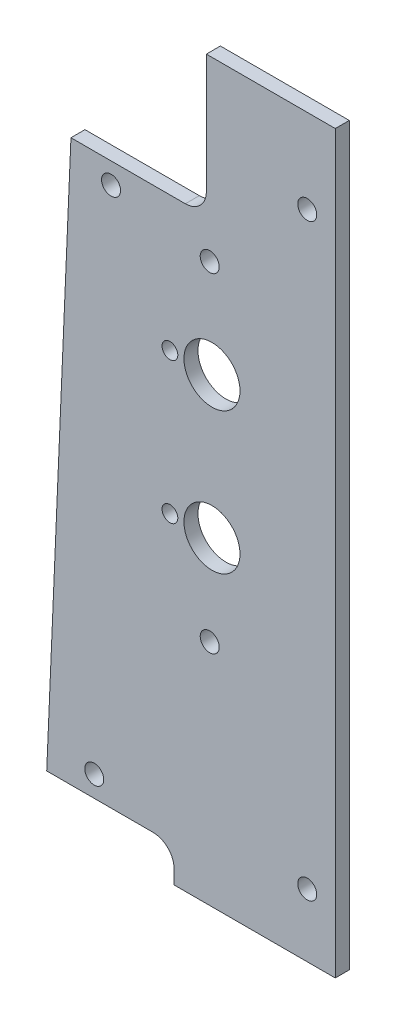
SolidWorks part; units mm, degrees
material "Acrylic (Medium-high impact)"
ref_plane "Front Plane" through (0, 0, 0) normal (0, 0, 1) x (1, 0, 0)
ref_plane "Top Plane" through (0, 0, 0) normal (0, 1, 0) x (1, 0, 0)
ref_plane "Right Plane" through (0, 0, 0) normal (1, 0, 0) x (0, 0, -1)
sketch "Sketch1" plane through (0, 0, 0) normal (0, 0, 1) x (1, 0, 0)
  line L8 (-36.5125, 0) -> (0, 0)
  line L9 (0, 0) -> (0, 166.6875)
  line L10 (0, 166.6875) -> (-29.21, 166.6875)
  line L11 (-29.21, 166.6875) -> (-29.21, 139.7)
  line L12 (-33.9725, 134.9375) -> (-59.8907, 134.9375)
  line L13 (-59.8907, 134.9375) -> (-65.3795, 7.9375)
  line L14 (-65.3795, 7.9375) -> (-41.275, 7.9375)
  line L15 (-36.5125, 3.175) -> (-36.5125, 0)
  line L16 (-36.5125, 0) -> (0, 0)
  line L17 (0, 0) -> (0, 166.6875)
  line L18 (0, 166.6875) -> (-29.21, 166.6875)
  line L19 (-29.21, 166.6875) -> (-29.21, 139.7)
  line L20 (-33.9725, 134.9375) -> (-59.8907, 134.9375)
  line L21 (-59.8907, 134.9375) -> (-65.3795, 7.9375)
  line L22 (-65.3795, 7.9375) -> (-41.275, 7.9375)
  line L23 (-36.5125, 3.175) -> (-36.5125, 0)
  arc A2 (-33.9725, 134.9375) -> (-29.21, 139.7) centre (-33.9725, 139.7) ccw
  arc A3 (-36.5125, 3.175) -> (-41.275, 7.9375) centre (-41.275, 3.175) ccw
  arc A4 (-33.9725, 134.9375) -> (-29.21, 139.7) centre (-33.9725, 139.7) ccw
  arc A5 (-36.5125, 3.175) -> (-41.275, 7.9375) centre (-41.275, 3.175) ccw
  dimension "D1" = 0
extrude "Boss-Extrude1" add sketch "Sketch1" against normal blind 3.175
hole_wizard "9/64 (0.14063) Diameter Hole1" positions "Sketch6" profile "Sketch5" hole size "9/64" standard "ANSI Inch" end condition through all
sketch "Sketch6" plane through (0, 0, 0) normal (0, 0, 1) x (1, 0, 0)
  point P0 (-18.415, 26.3525)
  point P3 (-37.465, 72.39)
  point P6 (-37.465, 104.394)
sketch "Sketch5" plane through (-18.415, 26.3525, 0) normal (1, 0, 0) x (0, -1, 0)
  line L0 (0, 0) -> (0, 3.175)
  line L1 (0, 3.175) -> (1.786, 3.175)
  line L2 (1.786, 3.175) -> (1.786, 0)
  line L5 (1.786, 0) -> (0, 0)
  line L11 (0, -6.35) -> (0, 107.95) construction
  dimension "Thru Hole Dia." = 3.572
  dimension "Thru Hole Depth" = 3.175
hole_wizard "1/2 (0.5) Diameter Hole1" positions "Sketch8" profile "Sketch7" hole size "1/2" standard "ANSI Inch" end condition through all
sketch "Sketch8" plane through (0, 0, 0) normal (0, 0, 1) x (1, 0, 0)
  point P0 (-27.94, 26.3525)
  point P3 (-27.94, 72.39)
  point P6 (-27.94, 104.394)
sketch "Sketch7" plane through (-27.94, 26.3525, 0) normal (1, 0, 0) x (0, -1, 0)
  line L0 (0, 0) -> (0, 3.175)
  line L1 (0, 3.175) -> (6.35, 3.175)
  line L2 (6.35, 3.175) -> (6.35, 0)
  line L5 (6.35, 0) -> (0, 0)
  line L11 (0, -6.35) -> (0, 107.95) construction
  dimension "Thru Hole Dia." = 12.7
  dimension "Thru Hole Depth" = 3.175
hole_wizard "#6 Clearance Hole1" positions "Sketch10" profile "Sketch9" hole size "#6" standard "ANSI Inch" end condition through all
sketch "Sketch10" plane through (0, 0, 0) normal (0, 0, 1) x (1, 0, 0)
  point P0 (-28.448, 51.7525)
  point P3 (-28.448, 126.365)
sketch "Sketch9" plane through (-28.448, 51.7525, 0) normal (1, 0, 0) x (0, -1, 0)
  line L0 (0, 0) -> (0, 3.175)
  line L1 (0, 3.175) -> (2.1526, 3.175)
  line L2 (2.1526, 3.175) -> (2.1526, 0)
  line L5 (2.1526, 0) -> (0, 0)
  line L11 (0, -6.35) -> (0, 107.95) construction
  dimension "Thru Hole Dia." = 4.3053
  dimension "Thru Hole Depth" = 3.175
hole_wizard "#6 Clearance Hole2" positions "Sketch12" profile "Sketch11" hole size "#6" standard "ANSI Inch" end condition through all
sketch "Sketch12" plane through (0, 0, 0) normal (0, 0, 1) x (1, 0, 0)
  point P0 (-50.8, 130.175)
  point P3 (-6.35, 147.6375)
  point P6 (-6.35, 14.2875)
  point P9 (-54.61, 12.7)
sketch "Sketch11" plane through (-50.8, 130.175, 0) normal (1, 0, 0) x (0, -1, 0)
  line L0 (0, 0) -> (0, 3.175)
  line L1 (0, 3.175) -> (2.1526, 3.175)
  line L2 (2.1526, 3.175) -> (2.1526, 0)
  line L5 (2.1526, 0) -> (0, 0)
  line L11 (0, -6.35) -> (0, 107.95) construction
  dimension "Thru Hole Dia." = 4.3053
  dimension "Thru Hole Depth" = 3.175
sketch "Sketch13" plane through (0, 0, 0) normal (0, 0, 1) x (1, 0, 0)
  line L1 (-36.7288, 18.4616) -> (-13.154, 18.4616)
  line L2 (-36.7288, 18.4616) -> (-36.7288, 34.3872)
  line L3 (-36.7288, 34.3872) -> (-13.154, 34.3872)
  line L4 (-13.154, 18.4616) -> (-13.154, 34.3872)
extrude "Boss-Extrude2" add sketch "Sketch13" against normal through all
